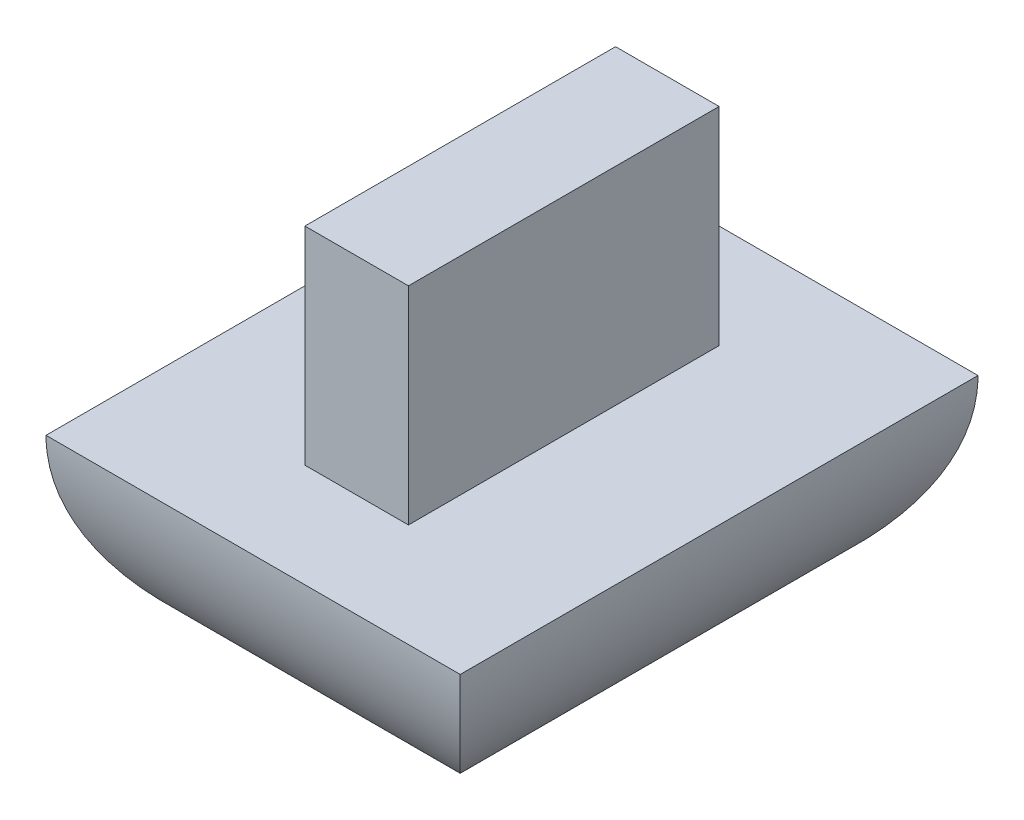
SolidWorks part; units mm, degrees
material "Silicon"
ref_plane "Front Plane" through (0, 0, 0) normal (0, 0, 1) x (1, 0, 0)
ref_plane "Top Plane" through (0, 0, 0) normal (0, 1, 0) x (1, 0, 0)
ref_plane "Right Plane" through (0, 0, 0) normal (1, 0, 0) x (0, 0, -1)
sketch "Sketch1" plane through (0, 0, 0) normal (0, 1, 0) x (1, 0, 0)
  line L0 (0, 3.9688) -> (6.35, 3.9688) construction
  line L1 (0, 0) -> (6.35, 0)
  line L2 (0, 0) -> (0, 7.9375)
  line L3 (0, 7.9375) -> (6.35, 7.9375)
  line L4 (6.35, 0) -> (6.35, 7.9375)
  line L6 (2.3813, 1.5875) -> (3.9688, 1.5875)
  line L7 (2.3813, 1.5875) -> (2.3813, 6.35)
  line L8 (2.3813, 6.35) -> (3.9688, 6.35)
  line L9 (3.9688, 1.5875) -> (3.9688, 6.35)
  line L10 (2.3813, 1.5875) -> (3.9688, 6.35) construction
  line L11 (2.3813, 6.35) -> (3.9688, 1.5875) construction
  point P7 (3.175, 3.9688)
  point P14 (3.175, 3.9688)
  dimension "D3" = 6.35
  dimension "D4" = 1.5875
  dimension "D5" = 7.9375
  dimension "D6" = 4.7625
extrude "Boss-Extrude1" add sketch "Sketch1" against normal blind 3.175 contours L1 L4 L3 L2 L9 L6 L7 L8 | L6 L9 L8 L7 region at (0.1016, 0, -3.9688) region at (3.175, 0, -3.9688)
extrude "Boss-Extrude2" add sketch "Sketch1<3>" along normal blind 3.175 contours L6 L9 L8 L7 region at (3.175, 0, -3.9688)
sketch "Sketch1<3>" plane through (0, 0, 0) normal (0, 1, 0) x (1, 0, 0) same geometry as "Sketch1"
fillet "Fillet1" radius 3.175 4 edges at (6.35, -3.175, -3.9688) (3.175, -3.175, -7.9375) (0, -3.175, -3.9688) (3.175, -3.175, 0)
